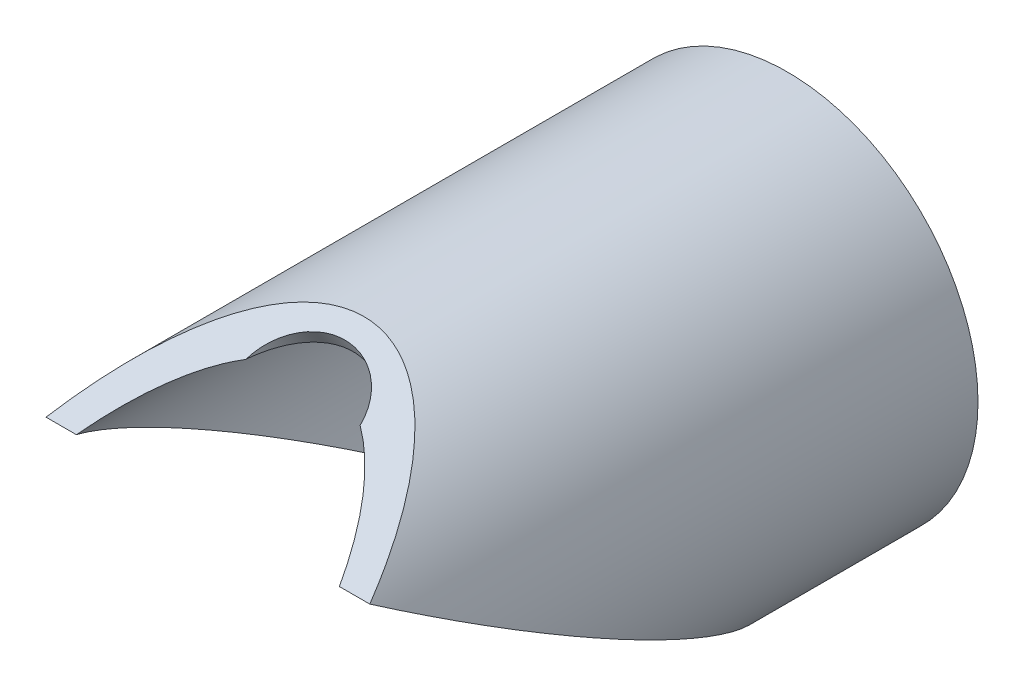
SolidWorks part; units mm, degrees
material "PVC Rigid"
ref_plane "Front Plane" through (0, 0, 0) normal (0, 0, 1) x (1, 0, 0)
ref_plane "Top Plane" through (0, 0, 0) normal (0, 1, 0) x (1, 0, 0)
ref_plane "Right Plane" through (0, 0, 0) normal (1, 0, 0) x (0, 0, -1)
sketch "Sketch1" plane through (0, 0, 0) normal (0, 0, 1) x (1, 0, 0)
  circle A0 centre (0, 0) radius 83.4771
  circle A2 centre (0, 0) radius 72.5043
  point P3 (0, 0)
  point P10 (0, 0)
  dimension "D1" = 10.9728
  dimension "D2" = 145.0086
extrude "Boss-Extrude1" add sketch "Sketch1" along normal blind 203.2 and the other way blind 177.8
sketch "Sketch14" plane through (0, 0, 0) normal (0, 0, 1) x (1, 0, 0)
  line L0 (152.4, 0) -> (-152.4, 0) construction
  point P5 (0, 0)
  dimension "D1" = 304.8
ref_axis "Axis1" through (-152.4, 0, 0) along (1, 0, 0)
ref_plane "Plane3" through (0, 0, 0) normal (0, 0.866, -0.5) x (-1, 0, 0)
sketch "Sketch8" plane through (0, 0, 0) normal (0, 0.866, -0.5) x (-1, 0, 0)
  line L1 (1016, -1016) -> (-1016, -1016)
  line L2 (1016, -1016) -> (1016, 1016)
  line L3 (1016, 1016) -> (-1016, 1016)
  line L4 (-1016, -1016) -> (-1016, 1016)
  line L5 (1016, -1016) -> (-1016, 1016) construction
  line L6 (1016, 1016) -> (-1016, -1016) construction
  point P0 (0, 0)
  dimension "D1" = 2032
  dimension "D2" = 2032
extrude "Cut-Extrude10" cut sketch "Sketch8" against normal blind 304.8
ref_plane "Plane4" through (0, 0, 0) normal (0, 0.866, 0.5) x (-1, 0, 0)
ref_plane "Plane5" through (0, 65.9911, 38.1) normal (0, 0.866, 0.5) x (-1, 0, 0)
sketch "Sketch17" plane through (0, 65.9911, 38.1) normal (0, 0.866, 0.5) x (-1, 0, 0)
  line L1 (101.6, 254) -> (-101.6, 254)
  line L2 (101.6, 254) -> (101.6, -254)
  line L3 (101.6, -254) -> (-101.6, -254)
  line L4 (-101.6, 254) -> (-101.6, -254)
  line L5 (101.6, 254) -> (-101.6, -254) construction
  line L6 (101.6, -254) -> (-101.6, 254) construction
  dimension "D1" = 203.2
  dimension "D2" = 508
extrude "Cut-Extrude14" cut sketch "Sketch17" along normal blind 152.4
sketch "Sketch18" plane through (0, 65.9911, 38.1) normal (0, 0.866, 0.5) x (1, 0, 0)
  circle A0 centre (0, 0) radius 25.4
  dimension "D1" = 50.8
extrude "Cut-Extrude15" cut sketch "Sketch18" against normal through all
